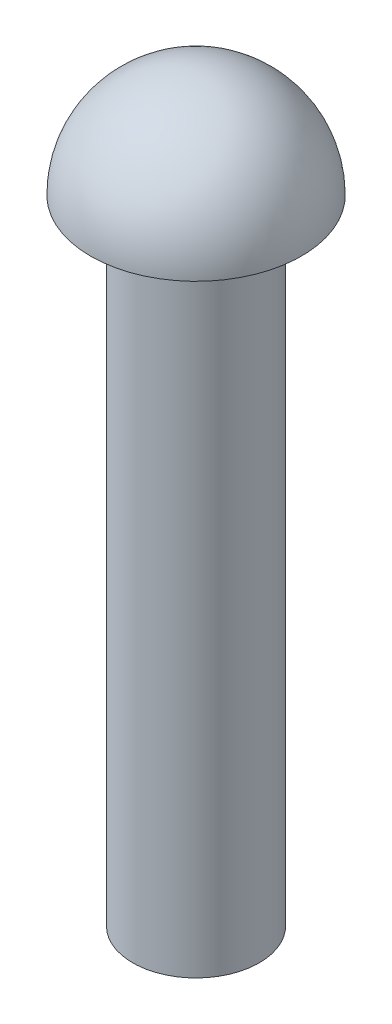
SolidWorks part; units mm, degrees
ref_plane "Front Plane" through (0, 0, 0) normal (0, 0, 1) x (1, 0, 0)
ref_plane "Top Plane" through (0, 0, 0) normal (0, 1, 0) x (1, 0, 0)
ref_plane "Right Plane" through (0, 0, 0) normal (1, 0, 0) x (0, 0, -1)
sketch "Sketch1" plane through (0, 0, 0) normal (0, 1, 0) x (1, 0, 0)
  circle A0 centre (0, 0) radius 3.81
  dimension "D1" = 7.62
extrude "Boss-Extrude1" add sketch "Sketch1" along normal blind 38.1
ref_point "Point1"
ref_axis "Axis1" through (0, 38.1, -4.318) along (0, 0, 1)
sketch "Sketch3" plane through (0, 0, 0) normal (1, 0, 0) x (0, 0, -1)
  line L0 (4.318, 38.1) -> (-6.858, 38.1) construction
  line L1 (0, 38.1) -> (6.35, 38.1)
  line L2 (0, 38.1) -> (0, 44.45)
  arc A0 (6.35, 38.1) -> (0, 44.45) centre (0, 38.1) ccw
  dimension "D1" = 6.35
  dimension "D2" = 90
  dimension "D3" = 0
ref_axis "Axis2" through (0, 38.1, 0) along (0, -1, 0)
revolve "Revolve3" add sketch "Sketch3" angle 360 about axis through (0, 38.1, 0) along (0, -1, 0)
